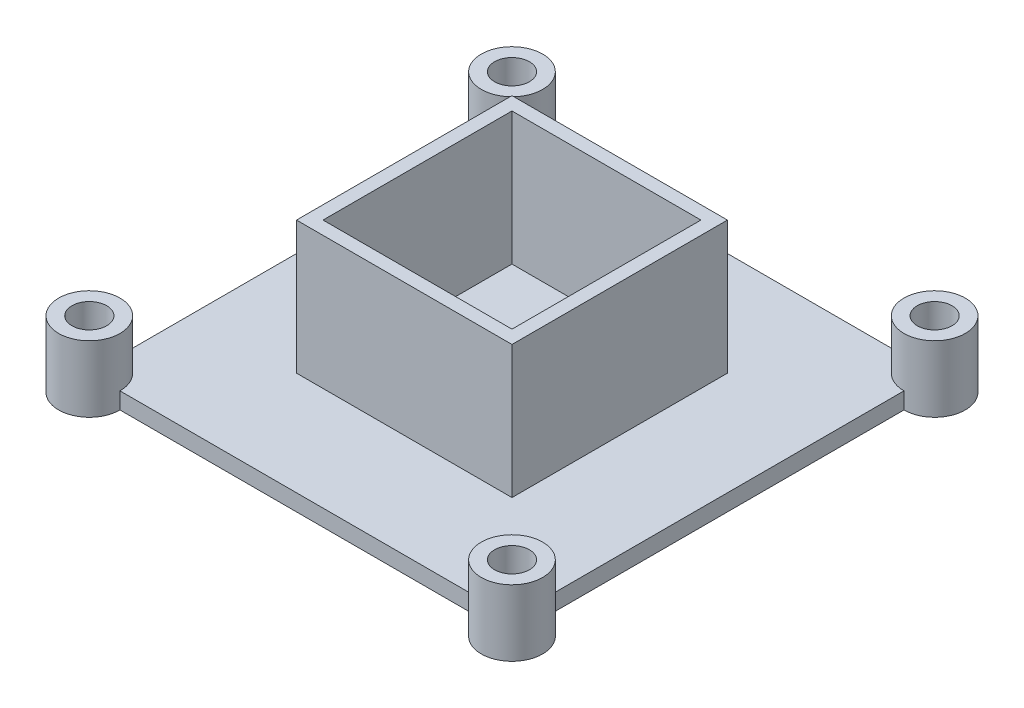
SolidWorks part; units mm, degrees
ref_plane "Front Plane" through (0, 0, 0) normal (0, 0, 1) x (1, 0, 0)
ref_plane "Top Plane" through (0, 0, 0) normal (0, 1, 0) x (1, 0, 0)
ref_plane "Right Plane" through (0, 0, 0) normal (1, 0, 0) x (0, 0, -1)
sketch "Sketch1" plane through (0, 0, 0) normal (0, 1, 0) x (1, 0, 0)
  line L1 (-10.5, -10.5) -> (15, -10.5)
  line L2 (-10.5, -10.5) -> (-10.5, 15)
  line L3 (-10.5, 15) -> (15, 15)
  line L4 (15, -10.5) -> (15, 15)
  circle A8 centre (-10.5, 15) radius 1.05
  circle A9 centre (15, 15) radius 1.05
  circle A10 centre (-10.5, -10.5) radius 1.05
  circle A11 centre (15, -10.5) radius 1.05
  circle A12 centre (-10.5, 15) radius 1.85
  circle A13 centre (15, 15) radius 1.85
  circle A14 centre (15, -10.5) radius 1.85
  circle A15 centre (-10.5, -10.5) radius 1.85
  point P0 (0, 0)
  point P6 (0, 0)
  dimension "D3" = 2.1
  dimension "D4" = 3.7
  dimension "D1" = 25.5
  dimension "D2" = 25.5
extrude "Boss-Extrude2" add sketch "Sketch1" against normal blind 1 contours A15 L1 A14 L4 A13 L3 A12 L2 | L2 A12 L3 A8 | L3 A12 L2 A8 | L2 A15 L1 A10 | L1 A15 L2 A10 | L1 A14 L4 A11 | L4 A14 L1 A11 | L4 A13 L3 A9 | L3 A13 L4 A9 | A14 | A11 region at (-9.5535, 0, 9.5535) region at (-9.05, 0, 10.5523) region at (2.25, 0, -2.25) region at (14.0535, 0, 9.5535) region at (13.55, 0, 10.5523) region at (-11.7711, 0, -16.2711) region at (-9.5535, 0, -14.0535) region at (14.0535, 0, -14.0535) region at (15.0523, 0, -13.55)
extrude "Boss-Extrude4" add sketch "Sketch1<5>" along normal blind 3 contours L4 A14 L1 A11 | L1 A14 L4 A11 | L3 A13 L4 A9 | L4 A13 L3 A9 | L1 A15 L2 A10 | L2 A15 L1 A10 | L3 A12 L2 A8 | L2 A12 L3 A8
sketch "Sketch1<5>" plane through (0, 0, 0) normal (0, 1, 0) x (1, 0, 0) same geometry as "Sketch1"
sketch "Sketch2" plane through (0, 0, 0) normal (0, 1, 0) x (1, 0, 0)
  line L0 (15, -10.5) -> (-10.5, 15) construction
  line L1 (15, 15) -> (-10.5, -10.5) construction
  line L2 (7.95, -3.45) -> (7.95, 7.95)
  line L3 (8.75, -4.25) -> (-4.25, -4.25)
  line L4 (8.75, -4.25) -> (8.75, 8.75)
  line L5 (8.75, 8.75) -> (-4.25, 8.75)
  line L6 (-4.25, -4.25) -> (-4.25, 8.75)
  line L7 (8.75, -4.25) -> (-4.25, 8.75) construction
  line L8 (8.75, 8.75) -> (-4.25, -4.25) construction
  line L9 (7.95, 7.95) -> (-3.45, 7.95)
  line L10 (-3.45, -3.45) -> (-3.45, 7.95)
  line L11 (7.95, -3.45) -> (-3.45, -3.45)
  point P7 (2.25, 2.25)
  dimension "D1" = 13
  dimension "D2" = 13
  dimension "D3" = 0.8
extrude "Boss-Extrude5" add sketch "Sketch2" along normal blind 8
